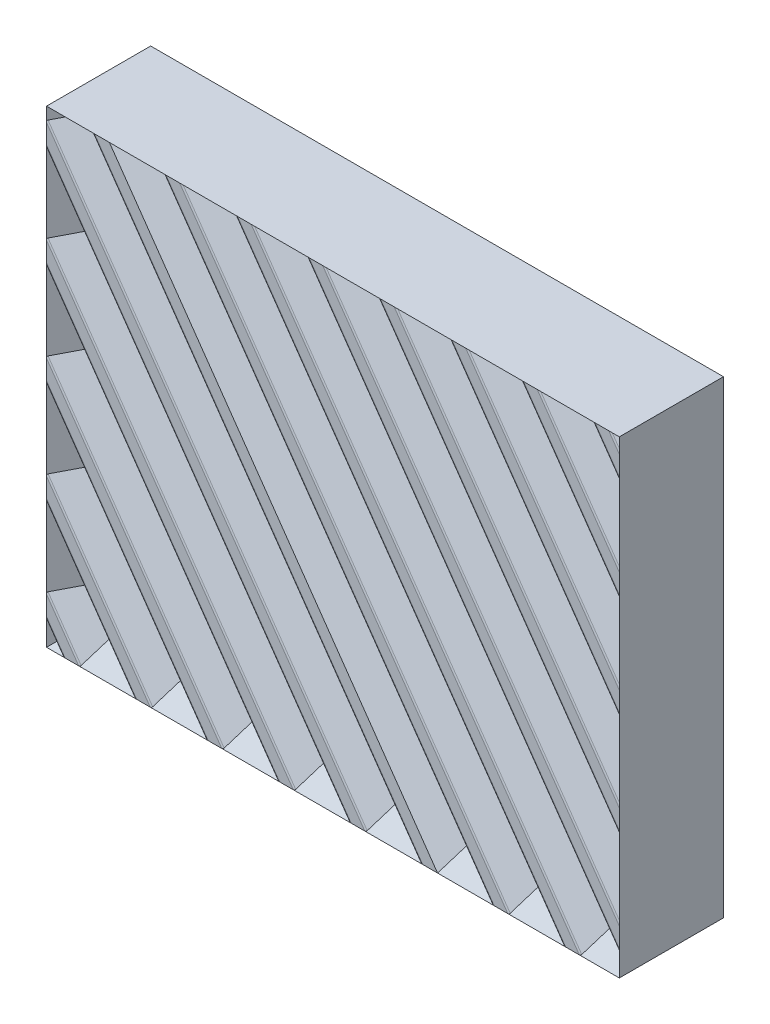
SolidWorks part; units mm, degrees
ref_plane "Front Plane" through (0, 0, 0) normal (0, 0, 1) x (1, 0, 0)
ref_plane "Top Plane" through (0, 0, 0) normal (0, 1, 0) x (1, 0, 0)
ref_plane "Right Plane" through (0, 0, 0) normal (1, 0, 0) x (0, 0, -1)
sketch "Sketch1" plane through (0, 0, 0) normal (0, 0, 1) x (1, 0, 0)
  line L1 (22, -18) -> (-22, -18)
  line L2 (22, -18) -> (22, 18)
  line L3 (22, 18) -> (-22, 18)
  line L4 (-22, -18) -> (-22, 18)
  line L5 (22, -18) -> (-22, 18) construction
  line L6 (22, 18) -> (-22, -18) construction
  point P0 (0, 0)
  dimension "D1" = 44
  dimension "D2" = 36
extrude "Boss-Extrude1" add sketch "Sketch1" along normal blind 8
sketch "Sketch2" plane through (0, 0, 8) normal (0, 0, 1) x (1, 0, 0)
  line L8 (-20, 16) -> (-20, -16)
  line L9 (-20, -16) -> (20, -16)
  line L10 (20, -16) -> (20, 16)
  line L11 (20, 16) -> (-20, 16)
  line L12 (-20, 16) -> (-20, -16)
  line L13 (-20, -16) -> (20, -16)
  line L14 (20, -16) -> (20, 16)
  line L15 (20, 16) -> (-20, 16)
  dimension "D1" = 2
extrude "Cut-Extrude1" cut sketch "Sketch2" against normal blind 2
sketch "Sketch3" plane through (0, 0, 6) normal (0, 0, 1) x (1, 0, 0)
  circle A0 centre (0, 0) radius 20
  line M6 (20, 16) -> (-20, 16)
  line M8 (-20, -16) -> (20, -16)
  dimension "D1" = 40
chamfer "Chamfer2" distance 2 angle 45 4 edges at (0, -16, 8) (20, 0, 8) (0, 16, 8) (-20, 0, 8)
extrude "Cut-Extrude2" cut sketch "Sketch3" against normal blind 5 contours A0 M6 M8 region at (0, 0, 6)
ref_plane "Plane1" through (15.695, -22.4148, 0) normal (0.5736, -0.8192, 0) x (0, 0, -1)
sketch "Sketch4" plane through (15.695, -22.4148, 0) normal (0.5736, -0.8192, 0) x (0, 0, -1)
  line L0 (-8, 27.7599) -> (-8, 26.3457)
  line L1 (-8, 7.697) -> (-8, 28.3457) construction
  line L2 (-8, 26.3457) -> (-6, 28.3457)
  line L3 (-6, 28.3457) -> (-6, 29.7599)
  line L4 (-6, 29.7599) -> (-8, 27.7599)
  dimension "D1" = 45
  dimension "D2" = 1
  dimension "D3" = 2
  dimension "D4" = 2
extrude "Boss-Extrude2" add sketch "Sketch4" against normal blind 60 and the other way blind 20
pattern_linear "LPattern1" count 13 spacing 4.5 along (-0.8192, -0.5736, 0) of "Boss-Extrude2"
sketch "Sketch5" plane through (0, 0, 0) normal (0, 0, -1) x (-1, 0, 0)
  line L4 (22, -18) -> (22, 18)
  line L5 (22, 18) -> (-22, 18)
  line L6 (-22, 18) -> (-22, -18)
  line L7 (-22, -18) -> (22, -18)
  line L8 (22, -18) -> (22, 18)
  line L9 (22, 18) -> (-22, 18)
  line L10 (-22, 18) -> (-22, -18)
  line L11 (-22, -18) -> (22, -18)
  dimension "D1" = 0
extrude "Cut-Extrude3" cut sketch "Sketch5" against normal through all flip side to cut
fillet "Fillet2" radius 0.2 26 edges at (21.6424, 17.4894, 8) (20.7792, 16.2566, 8) (18.8957, 13.5666, 8) (18.0325, 12.3338, 8) (16.149, 9.6438, 8) (15.2857, 8.411, 8) (13.4022, 5.7211, 8) (12.539, 4.4883, 8) (10.6555, 1.7983, 8) (9.7923, 0.5655, 8) (6.4212, 0, 8) (4.6948, 0, 8) (0.9277, 0, 8) (-0.7987, 0, 8) (-3.2796, -0.8156, 6) (-6.2922, 0, 8) (-9.7278, -0.4734, 8) (-10.591, -1.7062, 8) (-12.4745, -4.3962, 8) (-13.3377, -5.629, 8) (-15.2212, -8.3189, 8) (-16.0845, -9.5517, 8) (-17.968, -12.2417, 8) (-18.8312, -13.4745, 8) (-20.7147, -16.1645, 8) (-21.578, -17.3973, 8)
